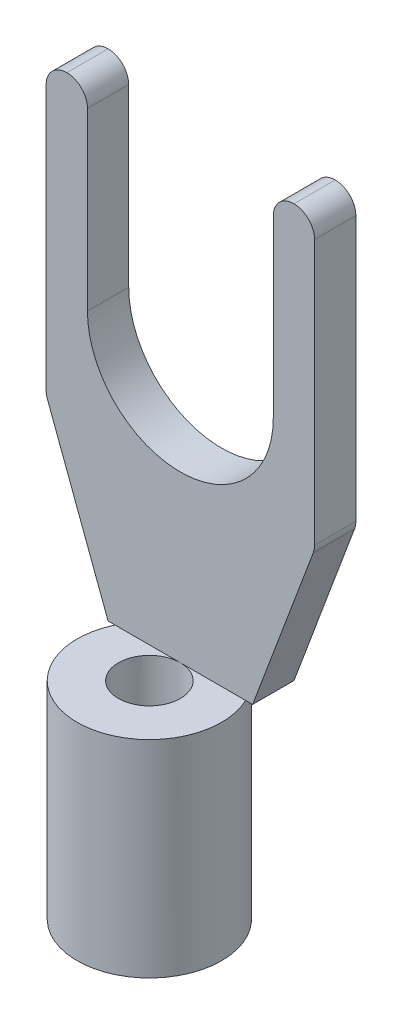
SolidWorks part; units mm, degrees
material "7075-T6, Platte (SS)"
ref_plane "Ebene vorne" through (0, 0, 0) normal (0, 0, 1) x (1, 0, 0)
ref_plane "Ebene oben" through (0, 0, 0) normal (0, 1, 0) x (1, 0, 0)
ref_plane "Ebene rechts" through (0, 0, 0) normal (1, 0, 0) x (0, 0, -1)
sketch "Skizze1" plane through (0, 0, 0) normal (0, 0, 1) x (1, 0, 0)
  line L0 (-3.25, 9) -> (-3.25, 2)
  line L1 (-3.25, 2) -> (3.25, 2) construction
  line L2 (-3.25, 2) -> (-3.25, -2) construction
  line L3 (-3.25, -2) -> (3.25, -2) construction
  line L4 (3.25, 2) -> (3.25, -2) construction
  line L5 (-3.25, 2) -> (3.25, -2) construction
  line L6 (-3.25, -2) -> (3.25, 2) construction
  line L7 (3.25, 2) -> (-3.25, 2) construction
  line L8 (3.25, 2) -> (3.25, 9) construction
  line L9 (3.25, 9) -> (-3.25, 9) construction
  line L10 (-3.25, 2) -> (-3.25, 9) construction
  line L11 (3.25, 2) -> (-3.25, 9) construction
  line L12 (3.25, 9) -> (-3.25, 2) construction
  line L13 (-1.75, 2) -> (1.75, 2) construction
  line L14 (-1.75, 2) -> (-1.75, -2) construction
  line L15 (-1.75, -2) -> (1.75, -2) construction
  line L16 (1.75, 2) -> (1.75, -2) construction
  line L17 (-1.75, 2) -> (1.75, -2) construction
  line L18 (-1.75, -2) -> (1.75, 2) construction
  line L19 (-3.25, 2) -> (-1.75, -2)
  line L20 (-1.75, -2) -> (1.75, -2)
  line L21 (1.75, -2) -> (3.25, 2)
  line L22 (3.25, 2) -> (3.25, 9)
  line L23 (0, 9) -> (0, 2) construction
  line L24 (-3.25, 9) -> (-2.25, 9)
  line L25 (-2.25, 9) -> (-2.25, 4.25)
  line L26 (-2.25, 4.25) -> (2.25, 4.25) construction
  line L27 (2.25, 4.25) -> (2.25, 9)
  line L28 (2.25, 9) -> (3.25, 9)
  arc A0 (-2.25, 4.25) -> (2.25, 4.25) centre (0, 4.25) ccw
  point P0 (0, 0)
  point P8 (0, 5.5)
  point P9 (0, 0)
  point P21 (0, 4.25)
  point P23 (0, 0)
  dimension "D1" = 4
  dimension "D2" = 7
  dimension "D3" = 6.5
  dimension "D4" = 3.5
  dimension "D5" = 1
extrude "Aufsatz-Linear austragen1" add sketch "Skizze1" along normal blind 1
fillet "Verrundung1" radius 0.5 6 edges at (-3.25, 2, 0.5) (3.25, 2, 0.5) (3.25, 9, 0.5) (2.25, 9, 0.5) (-2.25, 9, 0.5) (-3.25, 9, 0.5)
sketch "Skizze2" plane through (0, -2, 0) normal (0, -1, 0) x (1, 0, 0)
  line L0 (0, 0) -> (0, 1.75) construction
  line L1 (-1.75, 1) -> (1.75, 1) construction
  circle A0 centre (0, 1.75) radius 1.75
  circle A1 centre (0, 1.75) radius 0.75
  point P6 (0, 1)
  point P7 (0, 0)
  point P10 (0, 0)
  dimension "D1" = 1.5
extrude "Aufsatz-Linear austragen2" add sketch "Skizze2" along normal blind 5
